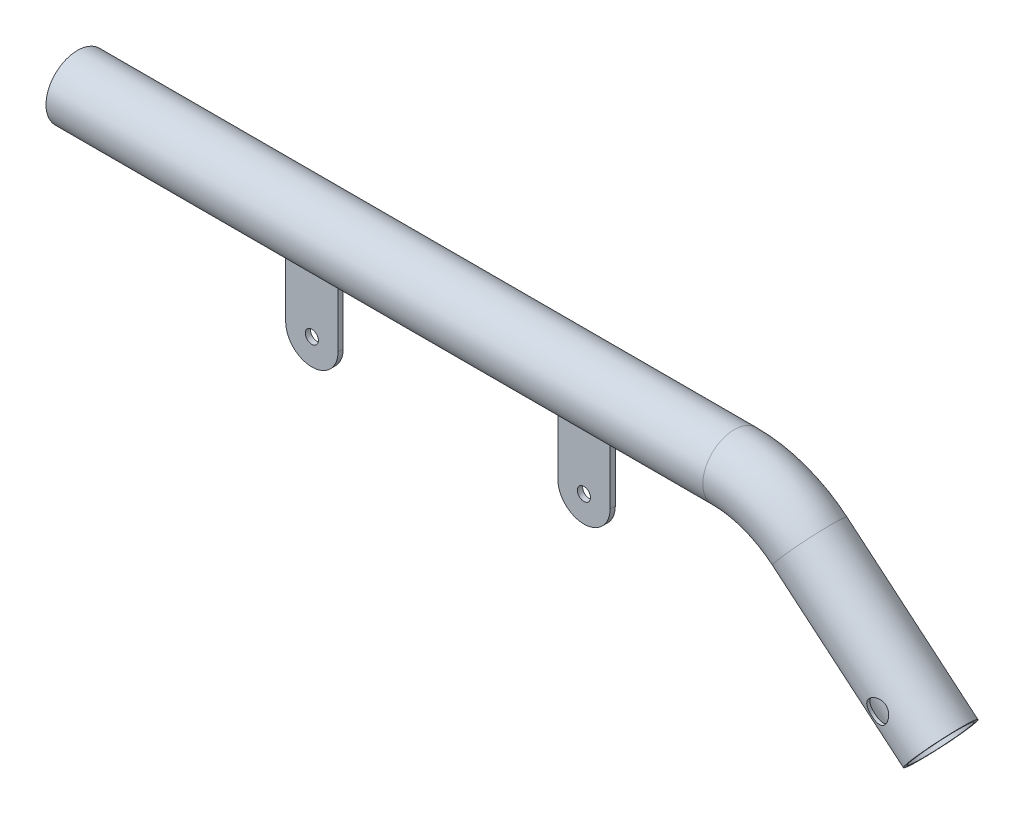
SolidWorks part; units mm, degrees
ref_plane "Front Plane" through (0, 0, 0) normal (0, 0, 1) x (1, 0, 0)
ref_plane "Top Plane" through (0, 0, 0) normal (0, 1, 0) x (1, 0, 0)
ref_plane "Right Plane" through (0, 0, 0) normal (1, 0, 0) x (0, 0, -1)
sketch "Sketch1" plane through (0, 0, 0) normal (0, 0, 1) x (1, 0, 0)
  line L0 (-209.3679, 0) -> (41.7067, 0)
  line L1 (70.6321, -10.528) -> (120.6321, -52.483)
  arc A0 (70.6321, -10.528) -> (41.7067, 0) centre (41.7067, -45) ccw
  dimension "D2" = 45
  dimension "D1" = 140
  dimension "D3" = 330
  dimension "D4" = 50
ref_plane "Plane1" through (-209.3679, 0, 0) normal (1, 0, 0) x (0, 0, -1)
sketch "Sketch2" plane through (-209.3679, 0, 0) normal (1, 0, 0) x (0, 0, -1)
  circle A0 centre (0, 0) radius 12
  circle A1 centre (0, 0) radius 10.8
  dimension "D1" = 1.2
sweep "Sweep1" add profiles "Sketch2" path "Sketch1"
sketch "Sketch3" plane through (0, 0, 0) normal (0, 0, 1) x (1, 0, 0)
  line L0 (120.6321, -52.483) -> (70.6321, -10.528) construction
  line L1 (112.9187, -61.6755) -> (128.3456, -43.2904) construction
  line L2 (78.3456, -1.3355) -> (62.9187, -19.7205) construction
  line L3 (-209.3679, 0) -> (41.7067, 0) construction
  line L4 (-209.3679, 12) -> (-209.3679, -12) construction
  line L5 (41.7067, 12) -> (41.7067, -12) construction
  circle A0 centre (108.2587, -42.1004) radius 4.1426
extrude "Cut-Extrude1" cut sketch "Sketch3" against normal blind 20 and the other way blind 20
sketch "Sketch4" plane through (0, 0, 0) normal (0, 0, 1) x (1, 0, 0)
  line L3 (-128.7413, 0) -> (-128.7413, -37)
  line L8 (-24.7413, 0) -> (-4.7413, 0)
  line L9 (-24.7413, 0) -> (-24.7413, -37)
  line L11 (-4.7413, 0) -> (-4.7413, -37)
  line L12 (-128.7413, 0) -> (-108.7413, 0)
  line L13 (-108.7413, 0) -> (-108.7413, -37)
  line L14 (-14.7413, 0) -> (-118.7413, 0) construction
  circle A0 centre (108.2587, -42.1004) radius 4.1426
  arc A1 (-24.7413, -37) -> (-4.7413, -37) centre (-14.7413, -37) ccw
  circle A2 centre (-14.7413, -37) radius 2.5
  arc A3 (-128.7413, -37) -> (-108.7413, -37) centre (-118.7413, -37) ccw
  circle A4 centre (-118.7413, -37) radius 2.5
  point P21 (-14.7413, 0)
  dimension "D3" = 123
  dimension "D1" = 20
  dimension "D2" = 37
  dimension "D4" = 104
  dimension "D5" = 37
extrude "Boss-Extrude1" add sketch "Sketch4" along normal blind 1 and the other way blind 1 contours L3 A3 L13 L12 | A1 L11 L8 L9 | A4 | A2
